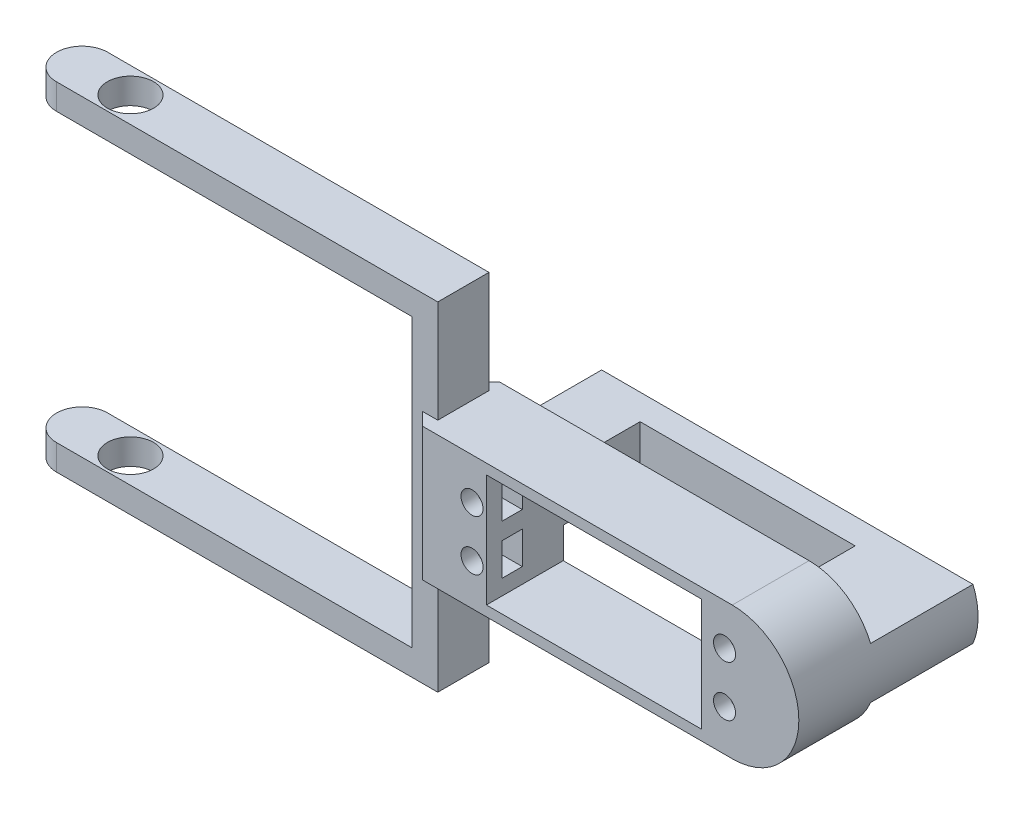
SolidWorks part; units mm, degrees
ref_plane "Plan de face" through (0, 0, 0) normal (0, 0, 1) x (1, 0, 0)
ref_plane "Plan de dessus" through (0, 0, 0) normal (0, 1, 0) x (1, 0, 0)
ref_plane "Plan de droite" through (0, 0, 0) normal (1, 0, 0) x (0, 0, -1)
sketch "Esquisse1" plane through (0, 0, 0) normal (0, 0, 1) x (1, 0, 0)
  line L1 (30, -13) -> (-30, -13)
  line L3 (30, 13) -> (-30, 13)
  line L4 (-30, -13) -> (-30, 13)
  line L5 (30, -13) -> (-30, 13) construction
  line L6 (30, 13) -> (-30, -13) construction
  arc A0 (30, -13) -> (30, 13) centre (30, 0) ccw
  point P0 (0, 0)
  dimension "D1" = 60
  dimension "D2" = 26
extrude "Boss.-Extru.1" add sketch "Esquisse1" along normal blind 15
sketch "Esquisse2" plane through (0, 0, 15) normal (0, 0, 1) x (1, 0, 0)
  line L0 (-30, 13) -> (-30, -13) construction
  line L1 (-18, 11) -> (24, 11)
  line L2 (-18, 11) -> (-18, -11)
  line L3 (-18, -11) -> (24, -11)
  line L4 (24, 11) -> (24, -11)
  point P4 (-18, 0)
  dimension "D1" = 42
  dimension "D2" = 22
  dimension "D3" = 12
extrude "Enlèv. mat.-Extru.1" cut sketch "Esquisse2" against normal through all
sketch "Esquisse4" plane through (0, 0, 15) normal (0, 0, 1) x (1, 0, 0)
  circle A0 centre (-20.81, 4.935) radius 2.15
  circle A1 centre (-20.81, -4.935) radius 2.15
  circle A2 centre (28.49, 4.935) radius 2.15
  circle A3 centre (28.49, -4.935) radius 2.15
extrude "Enlèv. mat.-Extru.2" cut sketch "Esquisse4" against normal blind 3
sketch "Esquisse5" plane through (-18, 0, 0) normal (1, 0, 0) x (0, 0, -1)
  line L1 (-12, -8) -> (-8, -8)
  line L2 (-12, -8) -> (-12, -1.65)
  line L3 (-12, -1.65) -> (-8, -1.65)
  line L4 (-8, -8) -> (-8, -1.65)
  line L5 (-15, 11) -> (-15, -11) construction
  line L6 (0, -11) -> (-15, -11) construction
  line L7 (-16.3207, 0) -> (1.751, 0) construction
  line L8 (-12, 1.65) -> (-8, 1.65)
  line L9 (-8, 8) -> (-8, 1.65)
  line L10 (-12, 8) -> (-8, 8)
  line L11 (-12, 8) -> (-12, 1.65)
  dimension "D1" = 6.35
  dimension "D2" = 4
  dimension "D3" = 3
  dimension "D4" = 3
extrude "Enlèv. mat.-Extru.3" cut sketch "Esquisse5" against normal blind 6
sketch "Esquisse6" plane through (24, 0, 0) normal (-1, 0, 0) x (0, 0, 1)
  line L0 (15, -11) -> (15, 11) construction
  line L1 (12, 8) -> (8, 8)
  line L2 (12, 8) -> (12, 1.65)
  line L3 (12, 1.65) -> (8, 1.65)
  line L4 (8, 8) -> (8, 1.65)
  line L5 (0, 11) -> (15, 11) construction
  line L6 (16.3207, 0) -> (-2.2889, 0) construction
  line L7 (12, -1.65) -> (8, -1.65)
  line L8 (8, -8) -> (8, -1.65)
  line L9 (12, -8) -> (8, -8)
  line L10 (12, -8) -> (12, -1.65)
  dimension "D1" = 6.35
  dimension "D2" = 4
  dimension "D3" = 3
  dimension "D4" = 3
extrude "Enlèv. mat.-Extru.4" cut sketch "Esquisse6" against normal blind 8
ref_plane "Plan1" through (0, 0, 7.5) normal (0, 0, 1) x (1, 0, 0)
sketch "Esquisse9" plane through (0, 0, 7.5) normal (0, 0, 1) x (1, 0, 0)
  line L0 (-30, -33) -> (-30, 33)
  line L1 (-30, 33) -> (-95, 33)
  line L2 (-95, 33) -> (-95, 28)
  line L3 (-95, 28) -> (-35, 28)
  line L4 (-35, 28) -> (-35, -28)
  line L5 (-21.7036, 0) -> (-118.5775, 0) construction
  line L6 (-95, -28) -> (-35, -28)
  line L7 (-30, -33) -> (-95, -33)
  line L8 (-95, -33) -> (-95, -28)
  line L10 (-30, 13) -> (-30, -13) construction
  point P9 (-30, 0)
  point P10 (-35, 0)
  point P12 (-30, 0)
  dimension "D1" = 28
  dimension "D2" = 5
  dimension "D3" = 5
  dimension "D4" = 65
extrude "Boss.-Extru.2" add sketch "Esquisse9" along normal blind 5 and the other way blind 5
chamfer "Chanfrein1" distance 3 angle 45 2 edges at (-30, 0, 12.5) (-30, 0, 2.5)
sketch "Esquisse11" plane through (0, -33, 0) normal (0, -1, 0) x (1, 0, 0)
  line L0 (-95, 2.5) -> (-95, 12.5)
  line L1 (-95, 2.5) -> (-104.4348, 2.5)
  line L2 (-95, 12.5) -> (-104.4348, 12.5)
  arc A1 (-104.4348, 2.5) -> (-104.4348, 12.5) centre (-104.4348, 7.5) cw
extrude "Boss.-Extru.4" add sketch "Esquisse11" against normal blind 5
sketch "Esquisse13" plane through (0, 0, 0) normal (0, 0, -1) x (-1, 0, 0)
  line L0 (18, 0) -> (30.5, 0) construction
  line L1 (18, 11) -> (18, -11) construction
  line L2 (30.5, -13) -> (30.5, 13) construction
  line L3 (-24, -11) -> (-24, 11) construction
  line L4 (30.5, -5) -> (18, -5)
  line L5 (30.5, -5) -> (30.5, 5)
  line L6 (30.5, 5) -> (18, 5)
  line L7 (18, -5) -> (18, 5)
  line L8 (30.5, -5) -> (18, 5) construction
  line L9 (30.5, 5) -> (18, -5) construction
  line L17 (18, 5) -> (-24, 5) construction
  line L18 (18, -5) -> (-24, -5) construction
  line L20 (-23.5605, 5) -> (-42, 5)
  line L21 (-24, -5) -> (-42, -5)
  line L22 (-24, 5) -> (-24, -5)
  arc A3 (-30, 13) -> (-30, -13) centre (-30, 0) ccw construction
  arc A4 (-42, 5) -> (-42, -5) centre (-30, 0) ccw
  point P6 (24.25, 0)
  line M10 (18, 11) -> (18, -11)
  line M12 (-24, -11) -> (-24, 11)
  line M14 (30.5, -13) -> (30.5, 13)
  arc M16 (-30, 13) -> (-30, -13) centre (-30, 0) ccw
  dimension "D1" = 10
extrude "Boss.-Extru.6" add sketch "Esquisse13" along normal blind 20 contours L21 L20 M12 M16 | L6 L4 M14 M10 region at (-24.25, 0, 0) region at (33.3383, 0, 0)
sketch "Esquisse14" plane through (0, 0, -20) normal (0, 0, -1) x (-1, 0, 0)
  line L1 (-24, 5) -> (18, 5)
  line L2 (-24, 5) -> (-24, -5)
  line L3 (-24, -5) -> (18, -5)
  line L4 (18, 5) -> (18, -5)
extrude "Boss.-Extru.7" add sketch "Esquisse14" against normal blind 5
sketch "Esquisse16" plane through (0, 33, 0) normal (0, 1, 0) x (1, 0, 0)
  line L0 (-35, -12.5) -> (-104.4348, -12.5) construction
  line L1 (-35, -2.5) -> (-104.4348, -2.5) construction
  line L2 (-89.416, -12.5) -> (-104.4348, -12.5)
  line L3 (-89.416, -2.5) -> (-104.4348, -2.5)
  line L4 (-89.416, -2.5) -> (-89.416, -12.5)
  arc A0 (-104.4348, -2.5) -> (-104.4348, -12.5) centre (-104.4348, -7.5) ccw construction
  arc A1 (-104.4348, -2.5) -> (-104.4348, -12.5) centre (-104.4348, -7.5) ccw
extrude "Boss.-Extru.8" add sketch "Esquisse16" against normal blind 5
sketch "Esquisse17" plane through (0, -33, 0) normal (0, -1, 0) x (1, 0, 0)
  circle A2 centre (-95, 7.5) radius 4.5
  arc A3 (-104.4348, 12.5) -> (-104.4348, 2.5) centre (-104.4348, 7.5) ccw construction
  dimension "D1" = 9
  dimension "D2" = 9.4348
extrude "Enlèv. mat.-Extru.5" cut sketch "Esquisse17" against normal through all
